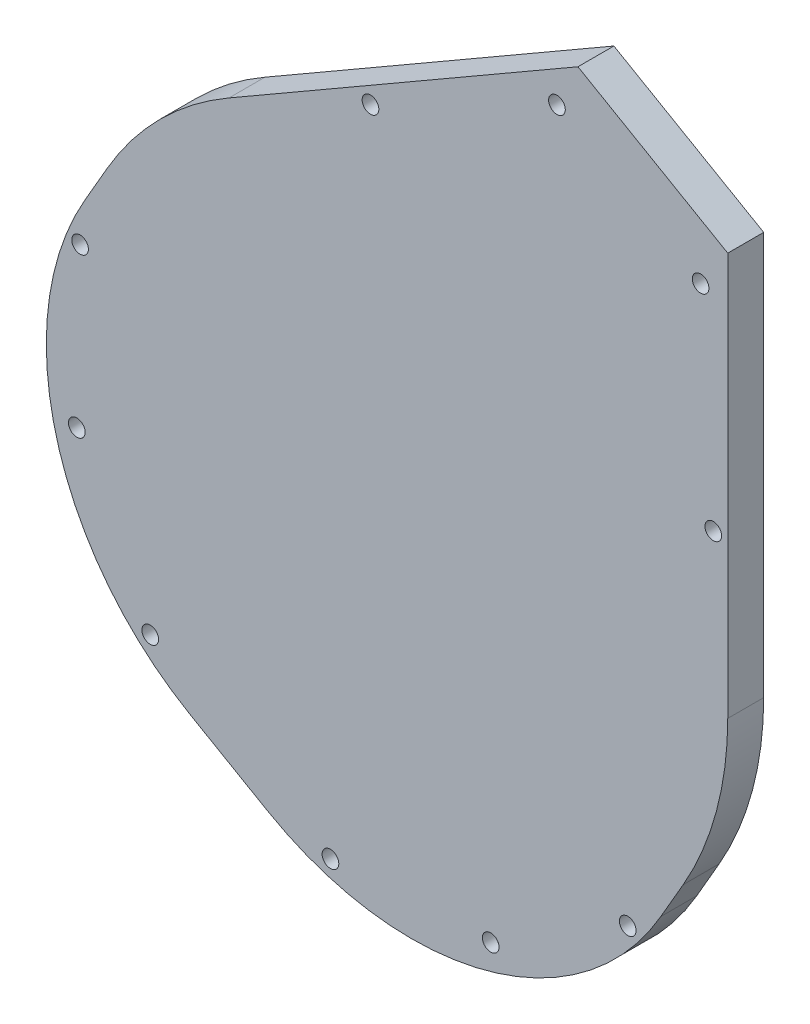
SolidWorks part; units mm, degrees
material "6061 Alloy"
ref_plane "Front Plane" through (0, 0, 0) normal (0, 0, 1) x (1, 0, 0)
ref_plane "Top Plane" through (0, 0, 0) normal (0, 1, 0) x (1, 0, 0)
ref_plane "Right Plane" through (0, 0, 0) normal (1, 0, 0) x (0, 0, -1)
sketch "Sketch3" plane through (0.1035, 1.9914, 0) normal (0, 0, 1) x (1, 0, 0)
  line L0 (-73.3817, 0) -> (87.2477, 0) construction
  line L1 (-41.9015, -72.5756) -> (73.9359, 128.0608) construction
  line L2 (58.7375, 0) -> (58.7375, 101.7363) construction
  line L3 (58.7375, 101.7363) -> (-29.3687, 50.8682) construction
  line L4 (18.1523, 85.445) -> (65.1899, 58.2878) construction
  line L5 (26.1049, 90.019) -> (66.8523, 66.4934) construction
  line L6 (58.7375, 0) -> (58.7375, 71.1785)
  line L7 (32.2737, 86.4574) -> (58.7375, 71.1785)
  line L8 (32.2737, 86.4574) -> (-29.3687, 50.8682)
  line L9 (-105.9419, -6.6586) -> (53.9719, -98.9849) construction
  line L10 (-80.2369, -21.4994) -> (-50.8682, 29.3688)
  line L11 (21.4994, -80.2369) -> (50.8682, -29.3687)
  line L12 (-80.2369, -21.4994) -> (21.4994, -80.2369)
  circle A0 centre (0, 0) radius 58.7375 construction
  circle A1 centre (36.7743, 63.695) radius 9.525 construction
  circle A2 centre (36.7743, 47.82) radius 6.35 construction
  circle A3 centre (0, 0) radius 50.8 construction
  arc A4 (-50.8682, 29.3688) -> (-29.3687, 50.8682) centre (0, 0) cw
  arc A6 (50.8682, -29.3687) -> (58.7375, 0) centre (0, 0) ccw
extrude "Boss-Extrude2" add sketch "Sketch3" along normal blind 6.35
hole_wizard "#4 Clearance Hole1" positions "Sketch5" profile "Sketch4" hole size "#4" standard "Ansi Inch" end condition through all
sketch "Sketch5" plane through (0, 0, 6.35) normal (0, 0, 1) x (1, 0, 0)
  circle A0 centre (28.6675, 80.7675) radius 1.1303 construction
  circle A1 centre (56.2828, 29.374) radius 1.1303 construction
  circle A2 centre (-4.2721, 64.3355) radius 1.1303 construction
  circle A4 centre (-55.571, 17.2749) radius 1.1303 construction
  circle A5 centre (41.1767, -38.5824) radius 1.1303 construction
  circle A6 centre (16.9659, -53.2254) radius 1.1303 construction
  circle A8 centre (-11.345, -54.5963) radius 1.1303 construction
  circle A9 centre (-56.1469, -11.0137) radius 1.1303 construction
  point P1 (28.6675, 80.7675)
  point P6 (54.0436, 66.1166)
  point P9 (-4.2721, 64.3355)
  point P12 (-55.571, 17.2749)
  point P15 (-56.1469, -11.0137)
  point P18 (-43.1787, -36.2172)
  point P21 (-11.345, -54.5963)
  point P24 (16.9659, -53.2254)
  point P27 (41.1767, -38.5824)
  point P30 (56.2828, 29.374)
sketch "Sketch4" plane through (28.6675, 80.7675, 6.35) normal (1, 0, 0) x (0, -1, 0)
  line L0 (0, 0) -> (0, 6.35)
  line L1 (0, 6.35) -> (1.4732, 6.35)
  line L2 (1.4732, 6.35) -> (1.4732, 0)
  line L5 (1.4732, 0) -> (0, 0)
  line L11 (0, -6.35) -> (0, 107.95) construction
  dimension "Thru Hole Dia." = 2.9464
  dimension "Thru Hole Depth" = 6.35
sketch "Sketch6" plane through (0.1035, 1.9914, 0) normal (0, 0, 1) x (1, 0, 0)
  line L0 (53.4662, 3.099) -> (49.8051, 63.4632)
  line L1 (30.0582, 74.8641) -> (-24.0493, 47.8526)
  line L4 (52.2998, 3.0299) -> (48.6397, 63.3794) construction
  line L5 (30.5684, 73.8129) -> (-23.526, 46.8079) construction
  line L6 (55.6721, 3.2299) -> (52.0095, 63.6203)
  line L7 (29.0921, 76.8517) -> (-25.0389, 49.8284)
  arc A0 (-24.0493, 47.8526) -> (53.4662, 3.099) centre (0, 0) ccw
  arc A1 (49.8051, 63.4632) -> (30.0582, 74.8641) centre (35.9806, 62.3202) ccw
  arc A4 (48.6397, 63.3794) -> (30.5684, 73.8129) centre (35.9806, 62.3202) ccw construction
  arc A5 (-23.526, 46.8079) -> (52.2998, 3.0299) centre (0, 0) ccw construction
  arc A6 (-25.0389, 49.8284) -> (55.6721, 3.2299) centre (0, 0) ccw
  arc A7 (52.0095, 63.6203) -> (29.0921, 76.8517) centre (35.9806, 62.3202) ccw
extrude "Cut-Extrude2 - dash 048" cut sketch "Sketch6" along normal blind 1.3208
fillet "Fillet1" radius 50.8 2 edges at (-80.1334, -19.508, 3.175) (21.6029, -78.2455, 3.175)
ref_plane "Plane1" through (-28.4806, -49.3298, 0) normal (-0.5, -0.866, 0) x (0.866, -0.5, 0)
ref_plane "Plane2" through (50.0835, -28.9157, 0) normal (0.866, -0.5, 0) x (0, 0, -1)
sketch3d "3DSketch1"
  point P0 (21.6029, -78.2455, 0)
